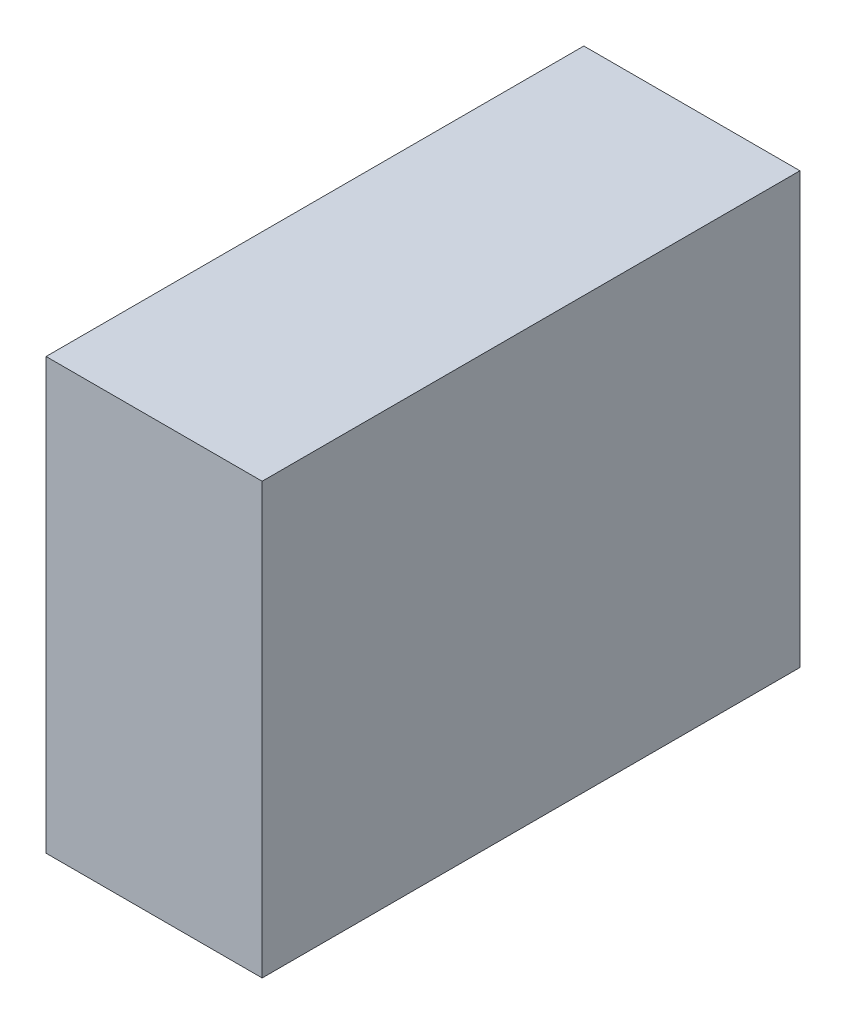
SolidWorks part; units mm, degrees
material "6061 Alloy"
ref_plane "Front Plane" through (0, 0, 0) normal (0, 0, 1) x (1, 0, 0)
ref_plane "Top Plane" through (0, 0, 0) normal (0, 1, 0) x (1, 0, 0)
ref_plane "Right Plane" through (0, 0, 0) normal (1, 0, 0) x (0, 0, -1)
sketch "Sketch1" plane through (0, 0, 0) normal (0, 0, 1) x (1, 0, 0)
  line L0 (0, 0) -> (2.0457, 0)
  line L1 (2.0457, 0) -> (2.0457, 8)
  line L2 (2.0457, 8) -> (-1.9726, 8)
  line L3 (-1.9726, 8) -> (-1.9726, 0)
  line L4 (-1.9726, 0) -> (0, 0)
  dimension "D1" = 8
  dimension "D2" = 2.0457
  dimension "D3" = 4.0183
extrude "Boss-Extrude1" add sketch "Sketch1" along normal blind 5 and the other way blind 5
